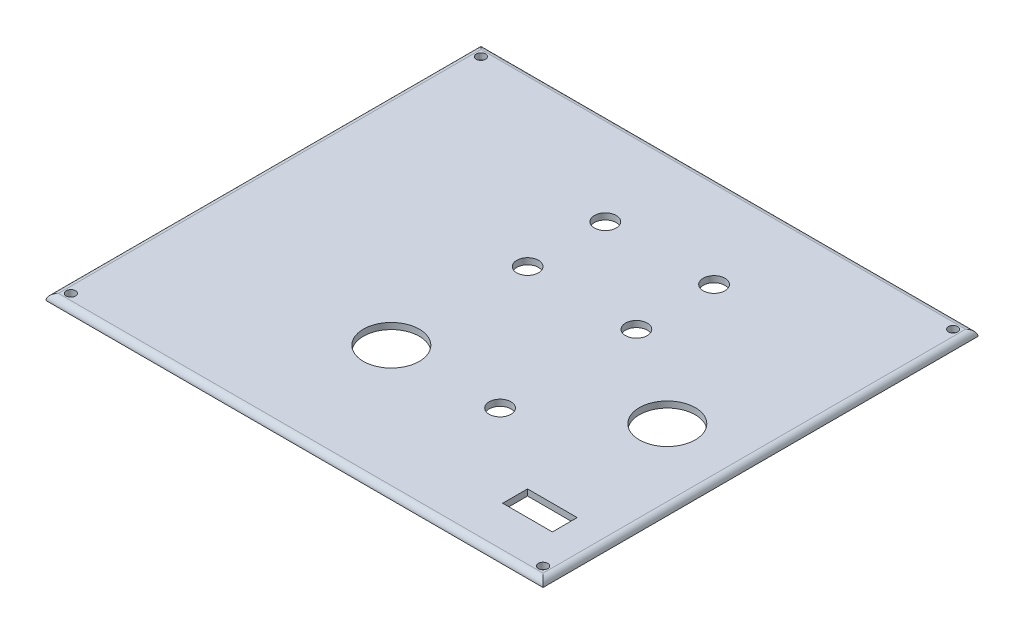
SolidWorks part; units mm, degrees
ref_plane "Front Plane" through (0, 0, 0) normal (0, 0, 1) x (1, 0, 0)
ref_plane "Top Plane" through (0, 0, 0) normal (0, 1, 0) x (1, 0, 0)
ref_plane "Right Plane" through (0, 0, 0) normal (1, 0, 0) x (0, 0, -1)
sketch "Sketch1" plane through (0, 0, 0) normal (0, 1, 0) x (1, 0, 0)
  line L1 (-80, 70) -> (80, 70)
  line L2 (-80, 70) -> (-80, -70)
  line L3 (-80, -70) -> (80, -70)
  line L4 (80, 70) -> (80, -70)
  line L5 (-80, 70) -> (80, -70) construction
  line L6 (-80, -70) -> (80, 70) construction
  point P0 (0, 0)
  dimension "D1" = 160
  dimension "D2" = 140
extrude "Boss-Extrude1" add sketch "Sketch1" along normal blind 2
sketch "Sketch2" plane through (0, 2, 0) normal (0, 1, 0) x (1, 0, 0)
  line L0 (80, 70) -> (-80, 70) construction
  line L1 (-80, 70) -> (-80, -70) construction
  line L2 (80, -70) -> (80, 70) construction
  line L3 (-80, -70) -> (80, -70) construction
  point P0 (-76, 66)
  point P1 (76, 66)
  point P2 (76, -66)
  point P3 (-76, -66)
  dimension "D1" = 4
  dimension "D2" = 4
  dimension "D3" = 4
  dimension "D4" = 4
hole_wizard "Ø3.0mm Dowel Hole1" positions "Sketch3" profile "Sketch4" hole size "Ø3.0" standard "ANSI Metric" end condition through all
sketch "Sketch3" plane through (0, 2, 0) normal (0, 1, 0) x (1, 0, 0)
  point P0 (-76, 66)
  point P3 (76, 66)
  point P6 (76, -66)
  point P9 (-76, -66)
sketch "Sketch4" plane through (-76, 2, -66) normal (1, 0, 0) x (0, 0, 1)
  line L0 (0, 0) -> (0, 2)
  line L1 (0, 2) -> (1.5, 2)
  line L2 (1.5, 2) -> (1.5, 0)
  line L5 (1.5, 0) -> (0, 0)
  line L11 (0, -6.35) -> (0, 107.95) construction
  dimension "Thru Hole Dia." = 3
  dimension "Thru Hole Depth" = 2
sketch "Sketch14" plane through (0, 2, 0) normal (0, 1, 0) x (1, 0, 0)
  line L1 (80, -70) -> (80, 70) construction
  line L2 (-80, -70) -> (80, -70) construction
  point P0 (56.336, -6.348)
  point P5 (-9.958, -28.878)
  dimension "D1" = 63.652
  dimension "D2" = 23.664
  dimension "D3" = 89.958
  dimension "D4" = 41.122
hole_wizard "Ø1.5mm Dowel Hole4" positions "Sketch15" profile "Sketch16" hole size "Ø1.5" standard "ANSI Metric" end condition through all
sketch "Sketch15" plane through (0, 2, 0) normal (0, 1, 0) x (1, 0, 0)
  point P0 (56.336, -6.348)
  point P3 (-9.958, -28.878)
sketch "Sketch16" plane through (56.336, 2, 6.348) normal (1, 0, 0) x (0, 0, 1)
  line L0 (0, 0) -> (0, 2)
  line L1 (0, 2) -> (9, 2)
  line L2 (9, 2) -> (9, 0)
  line L5 (9, 0) -> (0, 0)
  line L11 (0, -6.35) -> (0, 107.95) construction
  dimension "Thru Hole Dia." = 18
  dimension "Thru Hole Depth" = 2
sketch "Sketch17" plane through (0, 2, 0) normal (0, 1, 0) x (1, 0, 0)
  line L0 (80, 70) -> (-80, 70) construction
  point P0 (-9.958, 40)
  point P1 (25.042, 40)
  point P2 (25.042, 15)
  point P3 (-9.958, 15)
  point P4 (25.042, -28.878)
  dimension "D1" = 30
  dimension "D2" = 25
  dimension "D3" = 35
hole_wizard "Ø3.0mm Dowel Hole2" positions "Sketch20" profile "Sketch21" hole size "Ø3.0" standard "ANSI Metric" end condition through all
sketch "Sketch20" plane through (0, 2, 0) normal (0, 1, 0) x (1, 0, 0)
  point P0 (-9.958, 40)
  point P3 (25.042, 40)
  point P6 (-9.958, 15)
  point P9 (25.042, 15)
  point P12 (25.042, -28.878)
sketch "Sketch21" plane through (-9.958, 2, -40) normal (1, 0, 0) x (0, 0, 1)
  line L0 (0, 0) -> (0, 2)
  line L1 (0, 2) -> (3.5, 2)
  line L2 (3.5, 2) -> (3.5, 0)
  line L5 (3.5, 0) -> (0, 0)
  line L11 (0, -6.35) -> (0, 107.95) construction
  dimension "Thru Hole Dia." = 7
  dimension "Thru Hole Depth" = 2
fillet "Fillet2" radius 2 4 edges at (80, 2, 0) (0, 2, -70) (-80, 2, 0) (0, 2, 70)
sketch "Sketch22" plane through (0, 2, 0) normal (0, 1, 0) x (1, 0, 0)
  line L0 (78, -68) -> (78, 68) construction
  line L1 (52, -47) -> (68, -47)
  line L2 (52, -47) -> (52, -55)
  line L3 (52, -55) -> (68, -55)
  line L4 (68, -47) -> (68, -55)
  line L5 (52, -47) -> (68, -55) construction
  line L6 (52, -55) -> (68, -47) construction
  line L7 (-80, -70) -> (80, -70) construction
  point P0 (60, -51)
  point P5 (68, -51)
  dimension "D1" = 16
  dimension "D2" = 8
  dimension "D3" = 10
  dimension "D4" = 15
extrude "Cut-Extrude1" cut sketch "Sketch22" against normal blind 2
